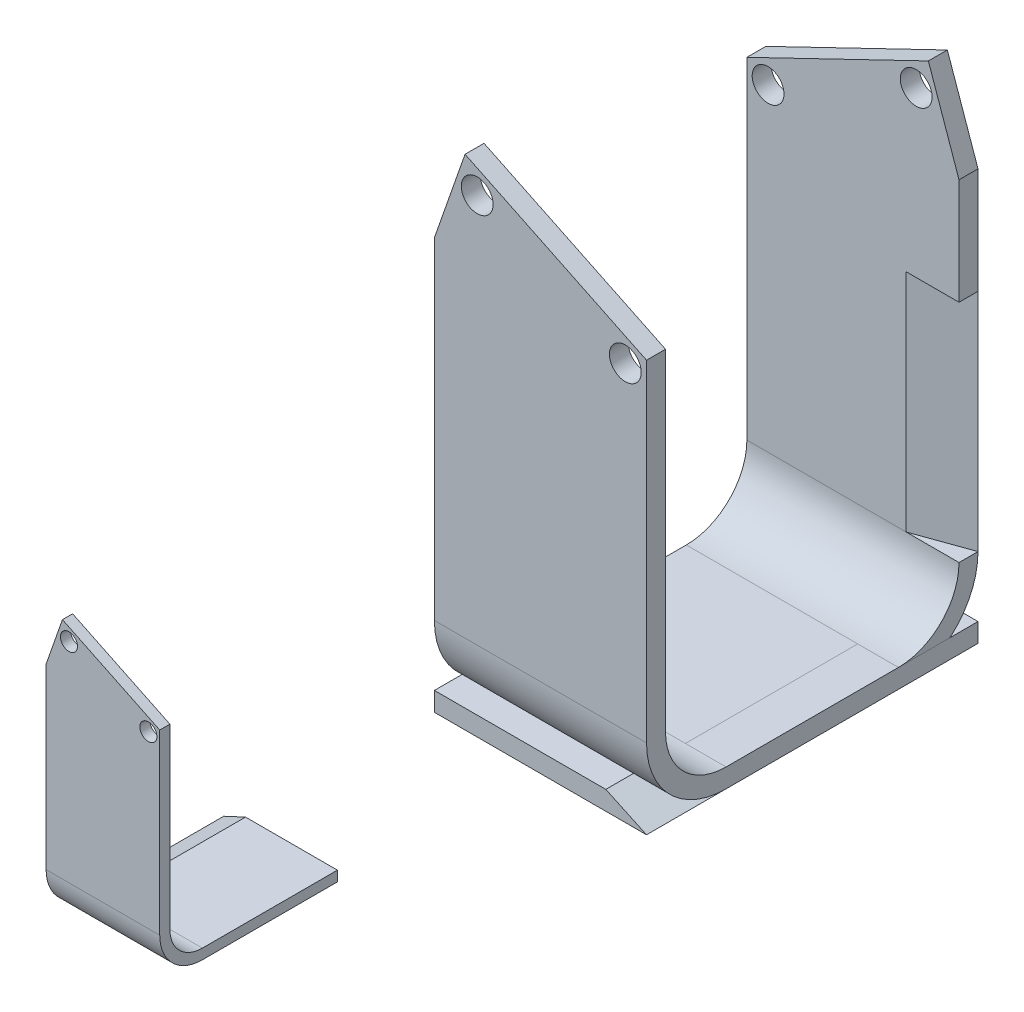
SolidWorks part; units mm, degrees
ref_plane "Front Plane" through (0, 0, 0) normal (0, 0, 1) x (1, 0, 0)
ref_plane "Top Plane" through (0, 0, 0) normal (0, 1, 0) x (1, 0, 0)
ref_plane "Right Plane" through (0, 0, 0) normal (1, 0, 0) x (0, 0, -1)
sketch "Sketch1" plane through (0, 0, 0) normal (1, 0, 0) x (0, 0, -1)
  line L0 (-43.0588, 0) -> (51.9412, 0)
  line L1 (81.9412, 30) -> (81.9412, 155)
  line L2 (-43.0588, 7.16) -> (51.9412, 7.16)
  line L3 (74.7812, 30) -> (74.7812, 155)
  line L4 (-43.0588, 0) -> (-43.0588, 7.16)
  line L5 (74.7812, 155) -> (81.9412, 155)
  arc A0 (51.9412, 0) -> (81.9412, 30) centre (51.9412, 30) ccw
  arc A1 (51.9412, 7.16) -> (74.7812, 30) centre (51.9412, 30) ccw
  point P6 (81.9412, 0)
  dimension "D3" = 30
  dimension "D1" = 125
  dimension "D2" = 155
  dimension "D4" = 7.16
extrude "Boss-Extrude1" add sketch "Sketch1" along normal blind 80
ref_plane "Plane1" through (0, 0, -74.7812) normal (0, 0, 1) x (1, 0, 0)
sketch "Sketch2" plane through (0, 0, -74.7812) normal (0, 0, 1) x (1, 0, 0)
  line L0 (0, 155) -> (68.4437, 188.0371)
  line L1 (68.4437, 188.0371) -> (80, 155)
  line L2 (80, 155) -> (0, 155)
  dimension "D1" = 76
  dimension "D2" = 35
extrude "Boss-Extrude2" add sketch "Sketch2" against normal blind 7.16
sketch "Sketch3" plane through (0, 0, -74.7812) normal (0, 0, 1) x (1, 0, 0)
  line L0 (80, 155) -> (68.4437, 188.0371) construction
  line L1 (68.4437, 188.0371) -> (0, 155) construction
  line L2 (0, 155) -> (0, 30) construction
  circle A0 centre (63.8512, 176.9371) radius 6
  circle A1 centre (8, 149.9783) radius 6
  dimension "D1" = 12
  dimension "D4" = 12
  dimension "D2" = 8
  dimension "D3" = 8
  dimension "D5" = 8
  dimension "D6" = 8
  dimension "D7" = 62.0172
  dimension "D8" = 62.0172
extrude "Cut-Extrude1" cut sketch "Sketch3" against normal blind 7.16 contours A0 | A1
sketch "Sketch4" plane through (0, 0, -74.7812) normal (0, 0, 1) x (1, 0, 0)
  line L0 (80, 155) -> (80, 115) construction
  line L1 (80, 155) -> (80, 30) construction
  dimension "D1" = 40
sketch "Sketch6" plane through (0, 0, 43.0588) normal (0, 0, 1) x (1, 0, 0)
  line L0 (80, 0) -> (64.6453, 7.16)
  line L1 (80, 7.16) -> (0, 7.16) construction
  line L2 (64.6453, 7.16) -> (80, 7.16)
  line L3 (80, 7.16) -> (80, 0)
  line L4 (80, 0) -> (0, 0) construction
  dimension "D1" = 25
extrude "Cut-Extrude6" cut sketch "Sketch6" against normal blind 95
sketch "Sketch8" plane through (80, 0, 0) normal (1, 0, 0) x (0, 0, -1)
  line L0 (74.7812, 115) -> (81.9412, 115)
  line L1 (81.9412, 30) -> (81.9412, 155) construction
sketch "Sketch9" plane through (0, 0, -74.7812) normal (0, 0, 1) x (1, 0, 0)
  line L0 (80, 115) -> (0, 115)
  line L1 (0, 155) -> (0, 30) construction
ref_plane "Plane2" through (0, 115, 0) normal (0, -1, 0) x (-1, 0, 0)
sketch "Sketch10" plane through (0, 115, 0) normal (0, -1, 0) x (-1, 0, 0)
  line L5 (-80, 81.9412) -> (-60, 74.7812)
  line L6 (-80, 74.7812) -> (-80, 81.9412) construction
  line L7 (-80, 74.7812) -> (0, 74.7812) construction
  line L8 (-60, 74.7812) -> (-80, 74.7812)
  line L9 (-80, 74.7812) -> (-80, 81.9412)
  dimension "D1" = 20
extrude "Cut-Extrude7" cut sketch "Sketch10" along normal blind 85
sketch "Sketch11" plane through (80, 0, 0) normal (1, 0, 0) x (0, 0, -1)
  line L2 (81.9412, 30) -> (74.7812, 30)
  line L3 (51.9412, 7.16) -> (51.9412, 0)
  line L4 (81.9412, 30) -> (74.7812, 30)
  line L5 (51.9412, 7.16) -> (51.9412, 0)
  arc A2 (51.9412, 7.16) -> (74.7812, 30) centre (51.9412, 30) ccw
  arc A3 (51.9412, 0) -> (81.9412, 30) centre (51.9412, 30) ccw
  arc A4 (51.9412, 7.16) -> (74.7812, 30) centre (51.9412, 30) ccw
  arc A5 (51.9412, 0) -> (81.9412, 30) centre (51.9412, 30) ccw
  dimension "D1" = 0
ref_plane "Plane3" through (-20, 0, 0) normal (-1, 0, 0) x (0, 0, 1)
move or copy body "Body-Move/Copy5" bodies to move or copy 109 copy yes number of copies 1 rotation origin (40, 0, -19.4412) rotation axis (0, 1, 0) rotation angle 180
move or copy body "Body-Move/Copy6" bodies to move or copy 118 copy yes number of copies 1 translate (0, 0, 180)
chamfer "Chamfer1" distance 7 angle 46 4 edges at (0, 8.7868, 214.272) (0, 13.8497, 209.2091) (0, 3.58, 193.0588) (0, 30, 219.4788)
scale "Scale1" bodies to scale 119 scale about centroid uniform scaling yes scale factor 0.714782
scale "Scale2" bodies to scale 120 scale about centroid uniform scaling yes scale factor 0.5
scale "Scale3" bodies to scale 121 scale about centroid uniform scaling yes scale factor 1.5
